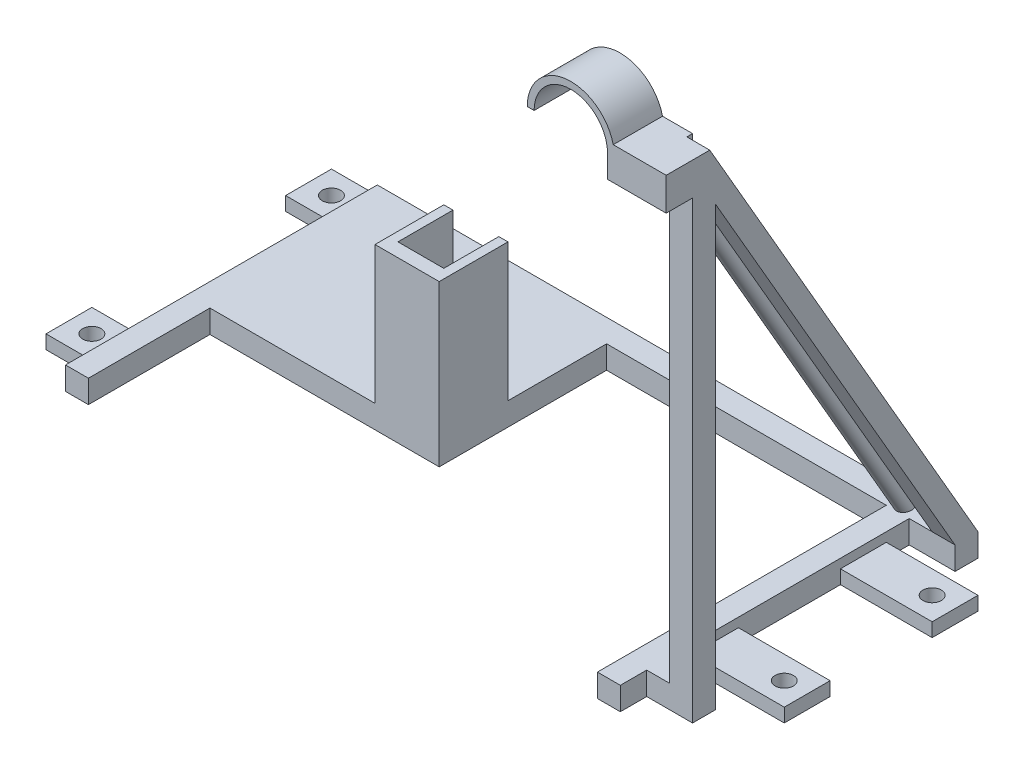
SolidWorks part; units mm, degrees
note: The reader was unsure of these and kept them because the rebuilt part matched: shared geometry of "Sketch23<2>".
ref_plane "Front Plane" through (0, 0, 0) normal (0, 0, 1) x (1, 0, 0)
ref_plane "Top Plane" through (0, 0, 0) normal (0, 1, 0) x (1, 0, 0)
ref_plane "Right Plane" through (0, 0, 0) normal (1, 0, 0) x (0, 0, -1)
sketch "Sketch1" plane through (0, 0, 0) normal (0, 1, 0) x (1, 0, 0)
  line L1 (0, 0) -> (121, 0)
  line L2 (0, 0) -> (0, -68)
  line L3 (0, -68) -> (121, -68)
  line L4 (121, 0) -> (121, -68)
  line L5 (5, -68) -> (116, -68)
  line L6 (5, -68) -> (5, -5)
  line L7 (5, -5) -> (116, -5)
  line L8 (116, -68) -> (116, -5)
  dimension "D1" = 121
  dimension "D2" = 68
  dimension "D3" = 5
  dimension "D4" = 5
  dimension "D5" = 5
extrude "Boss-Extrude1" add sketch "Sketch1" along normal blind 5 contours L8 L3 L4 L1 L2 L6 L7
ref_plane "Plane1" through (0, 3.75, 2.1651) normal (0, 0.866, 0.5) x (1, 0, 0)
sketch "Sketch2" plane through (0, 3.75, 2.1651) normal (0, 0.866, 0.5) x (1, 0, 0)
  line L2 (121, 2.5) -> (121, -56.3897) construction
  line L3 (0, 2.5) -> (121, 2.5) construction
  circle A0 centre (118.2001, -0.2999) radius 1.5
  dimension "D1" = 3
  dimension "D2" = 2.7999
  dimension "D3" = 2.7999
extrude "Boss-Extrude2" add sketch "Sketch2" along normal blind 100
ref_plane "Plane2" through (0, 0, 68) normal (0, 0, 1) x (1, 0, 0)
sketch "Sketch3" plane through (121, 0, 0) normal (1, 0, 0) x (0, 0, -1)
  line L0 (0, 5) -> (-68, 5) construction
  line L1 (0, 0) -> (-5, 0)
  line L2 (0, 0) -> (0, 5)
  line L3 (0, 5) -> (-5, 5)
  line L4 (-5, 0) -> (-5, 5)
  dimension "D1" = 5
extrude "Boss-Extrude3" add sketch "Sketch3" along normal blind 10
sketch "Sketch5" plane through (0, 3.75, 2.1651) normal (0, 0.866, 0.5) x (1, 0, 0)
  line L0 (131, -1.8301) -> (121, -1.8301) construction
  line L1 (131, 2.5) -> (126, 2.5)
  line L2 (131, 2.5) -> (131, -1.8301)
  line L3 (131, -1.8301) -> (126, -1.8301)
  line L4 (126, 2.5) -> (126, -1.8301)
  dimension "D1" = 5
extrude "Boss-Extrude4" add sketch "Sketch5" along normal offset from surface (117 mm away) 17 up to face at (118.2001, 89.4526, 53.7238) offset beyond the face yes
sketch "Sketch6" plane through (0, 1.25, -2.1651) normal (0, 0.5, -0.866) x (-1, 0, 0)
  line L0 (-126, 121.3301) -> (-126, 4.3301) construction
  line L1 (-131, 121.3301) -> (-126, 121.3301)
  line L2 (-131, 121.3301) -> (-131, 116.3301)
  line L3 (-131, 116.3301) -> (-126, 116.3301)
  line L4 (-126, 121.3301) -> (-126, 116.3301)
  dimension "D1" = 5
extrude "Boss-Extrude5" add sketch "Sketch6" along normal blind 20
sketch "Sketch7" plane through (126, 0, 0) normal (-1, 0, 0) x (0, 0, 1)
  line L0 (45.5096, 113.825) -> (41.1795, 116.325)
  line L1 (41.1795, 116.325) -> (62.25, 104.1599) construction
  line L2 (41.1795, 116.325) -> (38.6795, 111.9948)
  line L3 (38.6795, 111.9948) -> (43.0096, 109.4948)
  line L4 (38.6795, 111.9948) -> (56, 101.9948) construction
  line L5 (43.0096, 109.4948) -> (45.5096, 113.825)
  dimension "D1" = 90
  dimension "D2" = 5
extrude "Boss-Extrude6" add sketch "Sketch7" along normal blind 15
sketch "Sketch9" plane through (121, 0, 0) normal (1, 0, 0) x (0, 0, -1)
  line L0 (-62.25, 104.1599) -> (-62.25, 5) construction
  line L1 (-5, 5) -> (-68, 5) construction
  line L2 (-5, 0) -> (-68, 0) construction
  line L3 (-62.25, 5) -> (-57.25, 5)
  line L4 (-62.25, 5) -> (-62.25, 0)
  line L5 (-62.25, 0) -> (-57.25, 0)
  line L6 (-57.25, 5) -> (-57.25, 0)
  dimension "D1" = 5
extrude "Boss-Extrude7" add sketch "Sketch9" along normal up to surface (10 mm away) up to face at (131, 55.5593, 26.0136)
sketch "Sketch10" plane through (0, 5, 0) normal (0, 1, 0) x (1, 0, 0)
  line L0 (131, -57.25) -> (121, -57.25) construction
  line L1 (126, -57.25) -> (131, -57.25)
  line L2 (126, -57.25) -> (126, -62.25)
  line L3 (126, -62.25) -> (131, -62.25)
  line L4 (131, -57.25) -> (131, -62.25)
extrude "Boss-Extrude8" add sketch "Sketch10" along normal up to vertex
sketch "Sketch11" plane through (0, 0, 0) normal (-1, 0, 0) x (0, 0, 1)
  line L1 (62.25, 0) -> (52.25, 0)
  line L2 (62.25, 0) -> (62.25, 3)
  line L3 (62.25, 3) -> (52.25, 3)
  line L4 (52.25, 0) -> (52.25, 3)
  line L5 (0, 0) -> (10, 0)
  line L6 (0, 0) -> (0, 3)
  line L7 (0, 3) -> (10, 3)
  line L8 (10, 0) -> (10, 3)
  dimension "D1" = 10
  dimension "D2" = 3
  dimension "D3" = 10
  dimension "D4" = 3
extrude "Boss-Extrude9" add sketch "Sketch11" along normal blind 10
sketch "Sketch13" plane through (0, 3, 0) normal (0, 1, 0) x (1, 0, 0)
  line L0 (-5, -3) -> (-5, 0) construction
  line L1 (-10, 0) -> (0, 0) construction
  line L2 (-7, -5) -> (-10, -5) construction
  line L3 (-10, -10) -> (-10, 0) construction
  line L4 (-7, -57.25) -> (-10, -57.25) construction
  line L5 (-10, -62.25) -> (-10, -52.25) construction
  circle A0 centre (-5, -5) radius 2
  circle A1 centre (-5, -57.25) radius 2
  dimension "D1" = 4
extrude "Cut-Extrude1" cut sketch "Sketch13" against normal through all both and the other way through all
sketch "Sketch14" plane through (121, 0, 0) normal (1, 0, 0) x (0, 0, -1)
  line L0 (-5, 0) -> (-57.25, 0) construction
  line L1 (-20, 0) -> (-10, 0)
  line L2 (-20, 0) -> (-20, 3)
  line L3 (-20, 3) -> (-10, 3)
  line L4 (-10, 0) -> (-10, 3)
  line L5 (-57.25, 0) -> (-57.25, 5) construction
  line L6 (-42.25, 0) -> (-52.25, 0)
  line L7 (-42.25, 0) -> (-42.25, 3)
  line L8 (-42.25, 3) -> (-52.25, 3)
  line L9 (-52.25, 0) -> (-52.25, 3)
  line L10 (-5, 5) -> (-5, 0) construction
  dimension "D1" = 10
  dimension "D2" = 3
  dimension "D3" = 10
  dimension "D4" = 3
  dimension "D5" = 5
  dimension "D6" = 5
extrude "Boss-Extrude10" add sketch "Sketch14" along normal blind 20
sketch "Sketch15" plane through (0, 3, 0) normal (0, 1, 0) x (1, 0, 0)
  line L0 (138, -15) -> (141, -15) construction
  line L1 (141, -10) -> (141, -20) construction
  line L2 (136, -13) -> (136, -10) construction
  line L3 (141, -10) -> (121, -10) construction
  line L4 (136, -45.25) -> (136, -42.25) construction
  line L5 (141, -42.25) -> (121, -42.25) construction
  line L6 (138, -47.25) -> (141, -47.25) construction
  line L7 (141, -42.25) -> (141, -52.25) construction
  circle A0 centre (136, -15) radius 2
  circle A1 centre (136, -47.25) radius 2
  point P22 (141, -47.25)
  dimension "D1" = 4
extrude "Cut-Extrude2" cut sketch "Sketch15" against normal through all both and the other way through all
sketch "Sketch16" plane through (126, 0, 0) normal (-1, 0, 0) x (0, 0, 1)
  line L0 (49.8397, 111.325) -> (67, 101.4175)
  line L1 (49.8397, 111.325) -> (47.3397, 106.9948)
  line L2 (67, 101.4175) -> (64.5, 97.0874)
  line L3 (47.3397, 106.9948) -> (64.5, 97.0874)
  line L4 (45.5096, 113.825) -> (62.25, 104.1599) construction
  line L5 (43.0096, 109.4948) -> (56, 101.9948) construction
  line L6 (68, -54.223) -> (68, 54.223) construction
  line L7 (43.0096, 109.4948) -> (45.5096, 113.825) construction
  point P13 (44.2596, 111.6599)
  dimension "D1" = 1
  dimension "D2" = 90
  dimension "D3" = 5
extrude "Boss-Extrude11" add sketch "Sketch16" along normal blind 7.8
sketch "Sketch17" plane through (0, 105.075, 60.6651) normal (0, 0.866, 0.5) x (1, 0, 0)
  line L1 (131, 22.5) -> (108.821, 22.5)
  line L2 (131, 22.5) -> (131, 2.5)
  line L3 (131, 2.5) -> (108.821, 2.5)
  line L4 (108.821, 22.5) -> (108.821, 2.5)
  line L5 (0, 2.5) -> (126, 2.5) construction
extrude "Cut-Extrude3" cut sketch "Sketch17" against normal through all both and the other way through all
sketch "Sketch18" plane through (0, 0, 62.25) normal (0, 0, 1) x (1, 0, 0)
  line L0 (126, 104.1599) -> (118.2, 104.1599)
  line L1 (118.2, 104.1599) -> (102.2, 104.1599) construction
  line L2 (102.2, 104.1599) -> (100.7, 104.1599)
  arc A0 (102.2, 104.1599) -> (118.2, 104.1599) centre (110.2, 104.1599) cw
  arc A1 (100.7, 104.1599) -> (119.7, 104.1599) centre (110.2, 104.1599) cw
  dimension "D1" = 7.8
  dimension "D2" = 16
  dimension "D3" = 1.5
extrude "Boss-Extrude12" add sketch "Sketch18" along normal up to surface (5.75 mm away) and the other way blind 5 separate body contours A1 L2 A0 L0 up to plane "Plane2"
sketch "Sketch19" plane through (0, 104.1599, 0) normal (0, -1, 0) x (1, 0, 0)
  line L4 (119.7, 57.25) -> (119.7, 68)
  line L5 (119.7, 68) -> (118.2, 68)
  line L6 (118.2, 68) -> (118.2, 57.25)
  line L7 (118.2, 57.25) -> (119.7, 57.25)
  line L8 (119.7, 57.25) -> (119.7, 68)
  line L9 (119.7, 68) -> (118.2, 68)
  line L10 (118.2, 68) -> (118.2, 57.25)
  line L11 (118.2, 57.25) -> (119.7, 57.25)
  dimension "D1" = 0
extrude "Boss-Extrude13" add sketch "Sketch19" along normal up to vertex (2.7424 mm away) up to point (118.2, 101.4175, 67)
sketch "Sketch20" plane through (0, -3.6575, 6.3349) normal (0, -0.5, 0.866) x (1, 0, 0)
  line L5 (126, 116.3301) -> (126, 121.3301)
  line L6 (126, 121.3301) -> (119.7, 121.3301)
  line L7 (119.7, 121.3301) -> (118.2, 121.3301)
  line L8 (118.2, 121.3301) -> (118.2, 116.3301)
  line L9 (118.2, 116.3301) -> (126, 116.3301)
  line L10 (126, 116.3301) -> (126, 121.3301)
  line L11 (126, 121.3301) -> (119.7, 121.3301)
  line L12 (119.7, 121.3301) -> (118.2, 121.3301)
  line L13 (118.2, 121.3301) -> (118.2, 116.3301)
  line L14 (118.2, 116.3301) -> (126, 116.3301)
  dimension "D1" = 0
sketch "Sketch21" plane through (0, 101.4175, 0) normal (0, -1, 0) x (1, 0, 0)
  line L4 (118.2, 67) -> (119.7, 67)
  line L5 (119.7, 67) -> (119.7, 68)
  line L6 (119.7, 68) -> (118.2, 68)
  line L7 (118.2, 68) -> (118.2, 67)
  line L9 (119.7, 67) -> (119.7, 68)
  line L10 (119.7, 68) -> (118.2, 68)
  line L11 (118.2, 68) -> (118.2, 67)
  line L12 (118.2, 67) -> (119.7, 67)
  dimension "D1" = 0
extrude "Boss-Extrude15" add sketch "Sketch21" along normal blind 1
extrude "Boss-Extrude17" add sketch "Sketch20" against normal up to surface (1.1547 mm away)
ref_plane "Plane3" through (0, 104.1599, 0) normal (0, -1, 0) x (-1, 0, 0)
sketch "Sketch23" plane through (0, 104.1599, 0) normal (0, -1, 0) x (-1, 0, 0)
  line L1 (-126, -56) -> (-118.2, -56)
  line L2 (-126, -56) -> (-126, -68)
  line L3 (-126, -68) -> (-118.2, -68)
  line L4 (-118.2, -56) -> (-118.2, -68)
  dimension "D1" = 7.8
  dimension "D2" = 12
extrude "Cut-Extrude4" cut sketch "Sketch23" along normal blind 10 from offset 2
extrude "Boss-Extrude19" add sketch "Sketch23<2>" along normal blind 5 and the other way up to vertex (2.1651 mm away) other way up to point (119.45, 106.325, 58.5)
sketch "Sketch23<2>" plane through (0, 104.1599, 0) normal (0, -1, 0) x (-1, 0, 0) same geometry as "Sketch23"
sketch "Sketch24" plane through (0, 0, 56) normal (0, 0, -1) x (-1, 0, 0)
  line L5 (-126, 106.325) -> (-126, 101.9948)
  line L6 (-126, 101.9948) -> (-126, 99.1599)
  line L7 (-126, 99.1599) -> (-118.2, 99.1599)
  line L8 (-118.2, 99.1599) -> (-118.2, 106.325)
  line L9 (-118.2, 106.325) -> (-126, 106.325)
  line L10 (-126, 106.325) -> (-126, 101.9948)
  line L11 (-126, 101.9948) -> (-126, 99.1599)
  line L12 (-126, 99.1599) -> (-118.2, 99.1599)
  line L13 (-118.2, 99.1599) -> (-118.2, 106.325)
  line L14 (-118.2, 106.325) -> (-126, 106.325)
  dimension "D1" = 0
extrude "Cut-Extrude5" cut sketch "Sketch24" against normal up to surface (1.25 mm away) up to face at (111.5571, 108.2969, 57.25)
sketch "Sketch25" plane through (0, 105.075, 60.6651) normal (0, 0.866, 0.5) x (1, 0, 0)
  line L4 (126, 2.5) -> (126, -1.8301)
  line L5 (126, -1.8301) -> (131, -1.8301)
  line L6 (131, -1.8301) -> (131, 2.5)
  line L7 (131, 2.5) -> (126, 2.5)
  line L8 (126, 2.5) -> (126, -1.8301)
  line L9 (126, -1.8301) -> (131, -1.8301)
  line L10 (131, -1.8301) -> (131, 2.5)
  line L11 (131, 2.5) -> (126, 2.5)
  dimension "D1" = 0
extrude "Boss-Extrude20" add sketch "Sketch25" along normal up to surface (2.5 mm away) up to face at (123.38, 106.325, 61.8)
sketch "Sketch26" plane through (0, 0, 62.25) normal (0, 0, 1) x (1, 0, 0)
  line L1 (131, 104.1599) -> (126, 104.1599)
  line L2 (131, 104.1599) -> (131, 106.325)
  line L3 (131, 106.325) -> (126, 106.325)
  line L4 (126, 104.1599) -> (126, 106.325)
extrude "Cut-Extrude6" cut sketch "Sketch26" along normal blind 5
sketch "Sketch27" plane through (126, 0, 0) normal (1, 0, 0) x (0, 0, -1)
  line L4 (-62.25, 99.1599) -> (-62.25, 106.325)
  line L5 (-62.25, 106.325) -> (-68, 106.325)
  line L6 (-68, 106.325) -> (-68, 99.1599)
  line L7 (-68, 99.1599) -> (-62.25, 99.1599)
  line L8 (-62.25, 99.1599) -> (-62.25, 106.325)
  line L9 (-62.25, 106.325) -> (-68, 106.325)
  line L10 (-68, 106.325) -> (-68, 99.1599)
  line L11 (-68, 99.1599) -> (-62.25, 99.1599)
  dimension "D1" = 0
extrude "Boss-Extrude21" add sketch "Sketch27" along normal up to surface (5 mm away) up to face at (131, 35.35, 34.1667)
sketch "Sketch29" plane through (0, 0, 0) normal (-1, 0, 0) x (0, 0, 1)
  line L0 (26, 0) -> (26, 35) construction
  line L1 (10, 0) -> (52.25, 0) construction
  line L2 (0, 5) -> (0, 3) construction
  line L3 (0, 5) -> (68, 5) construction
  line L4 (38.5, 5) -> (38.5, 35)
  line L6 (38.5, 35) -> (41.5, 35)
  line L7 (38.5, 35) -> (38.5, 5)
  line L8 (38.5, 5) -> (41.5, 5)
  line L9 (41.5, 35) -> (41.5, 5)
  line M7 (68, 5) -> (0, 5)
  dimension "D1" = 30
  dimension "D2" = 26
  dimension "D3" = 35
  dimension "D4" = 12.5
  dimension "D5" = 12.5
  dimension "D6" = 3
extrude "Boss-Extrude22" add sketch "Sketch29" against normal blind 55 contours L9 L6 L4 M7
sketch "Sketch30" plane through (0, 5, 0) normal (0, -1, 0) x (1, 0, 0)
  line L0 (55, 41.5) -> (5, 41.5) construction
  line L1 (55, 38.5) -> (50, 38.5)
  line L2 (55, 38.5) -> (55, 41.5)
  line L3 (55, 41.5) -> (50, 41.5)
  line L4 (50, 38.5) -> (50, 41.5)
  dimension "D1" = 5
extrude "Boss-Extrude23" add sketch "Sketch30" along normal up to surface (5 mm away) up to face at (136, 0, 17)
sketch "Sketch31" plane through (0, 0, 38.5) normal (0, 0, -1) x (-1, 0, 0)
  line L0 (10, 0) -> (-131, 0) construction
  line L1 (-50, 5) -> (-55, 5)
  line L2 (-50, 5) -> (-50, 0)
  line L3 (-50, 0) -> (-55, 0)
  line L4 (-55, 5) -> (-55, 0)
  line L5 (-55, 0) -> (-55, 35) construction
extrude "Boss-Extrude24" add sketch "Sketch31" along normal up to surface (33.5 mm away) up to face at (60.5, 2.5, 5)
sketch "Sketch32" plane through (0, 0, 38.5) normal (0, 0, -1) x (-1, 0, 0)
  line L0 (-53, 9) -> (-41, 9)
  line L1 (-55, 35) -> (-55, 7)
  line L2 (-53, 35) -> (-57, 35)
  line L3 (-57, 35) -> (-57, 9)
  line L4 (-41, 7) -> (-69, 7)
  line L5 (-67, 35) -> (-67, 16)
  line L6 (-67, 35) -> (-69, 35)
  line L7 (-69, 35) -> (-69, 16)
  line L8 (-67, 16) -> (-69, 16)
  line L10 (-41, 7) -> (-41, 9)
  line L13 (-69, 7) -> (-69, 9)
  line L14 (-57, 9) -> (-69, 9)
  line L16 (-43, 16) -> (-41, 16)
  line L17 (-41, 35) -> (-41, 16)
  line L18 (-43, 35) -> (-41, 35)
  line L19 (-43, 35) -> (-43, 16)
  line L20 (-53, 35) -> (-53, 9)
  point P4 (0, 0)
  point P21 (0, 0)
  point P22 (0, 0)
  point P23 (-34.1368, 7)
  line M7 (0, 35) -> (-55, 35)
  line M8 (-55, 35) -> (-55, 5)
  dimension "D2" = 10
  dimension "D3" = 2
  dimension "D4" = 19
extrude "Boss-Extrude25" add sketch "Sketch32" along normal blind 12 contours L20 L4 L10 L0 M7 M8 | L19 L16 L17 M7
sketch "Sketch34" plane through (0, 35, 0) normal (0, 1, 0) x (1, 0, 0)
  line L1 (41, -38.5) -> (0, -38.5)
  line L2 (41, -38.5) -> (41, -41.5)
  line L3 (41, -41.5) -> (0, -41.5)
  line L4 (0, -38.5) -> (0, -41.5)
extrude "Cut-Extrude7" cut sketch "Sketch34" against normal up to surface (30 mm away) up to face at (118.2001, 5, 1.501)
sketch "Sketch35" plane through (0, 7, 0) normal (0, -1, 0) x (1, 0, 0)
  line L4 (55, 38.5) -> (41, 38.5)
  line L5 (41, 38.5) -> (41, 26.5)
  line L6 (41, 26.5) -> (55, 26.5)
  line L7 (55, 26.5) -> (55, 38.5)
  line L8 (55, 38.5) -> (41, 38.5)
  line L9 (41, 38.5) -> (41, 26.5)
  line L10 (41, 26.5) -> (55, 26.5)
  line L11 (55, 26.5) -> (55, 38.5)
  dimension "D1" = 0
extrude "Boss-Extrude26" add sketch "Sketch35" along normal up to surface (7 mm away) up to face at (136, 0, 17)
sketch "Sketch36" plane through (0, 0, 38.5) normal (0, 0, 1) x (1, 0, 0)
  line L4 (50, 0) -> (50, 5)
  line L5 (50, 5) -> (41, 5)
  line L6 (41, 5) -> (41, 0)
  line L7 (41, 0) -> (50, 0)
  line L8 (50, 0) -> (50, 5)
  line L9 (50, 5) -> (41, 5)
  line L10 (41, 5) -> (41, 0)
  line L11 (41, 0) -> (50, 0)
  dimension "D1" = 0
extrude "Boss-Extrude27" add sketch "Sketch36" along normal up to surface and the other way up to surface up to face at (48.6667, 13.3333, 41.5) other way up to face at (27.5, 2.5, 5)
sketch "Sketch37" plane through (41, 0, 0) normal (-1, 0, 0) x (0, 0, 1)
  line L1 (41.5, 0) -> (0, 0)
  line L2 (41.5, 0) -> (41.5, 5)
  line L3 (41.5, 5) -> (0, 5)
  line L4 (0, 0) -> (0, 5)
extrude "Boss-Extrude28" add sketch "Sketch37" along normal up to surface (41 mm away) contours L2 L1 L4 L3 up to face at (0, 2.2, 38.5)
